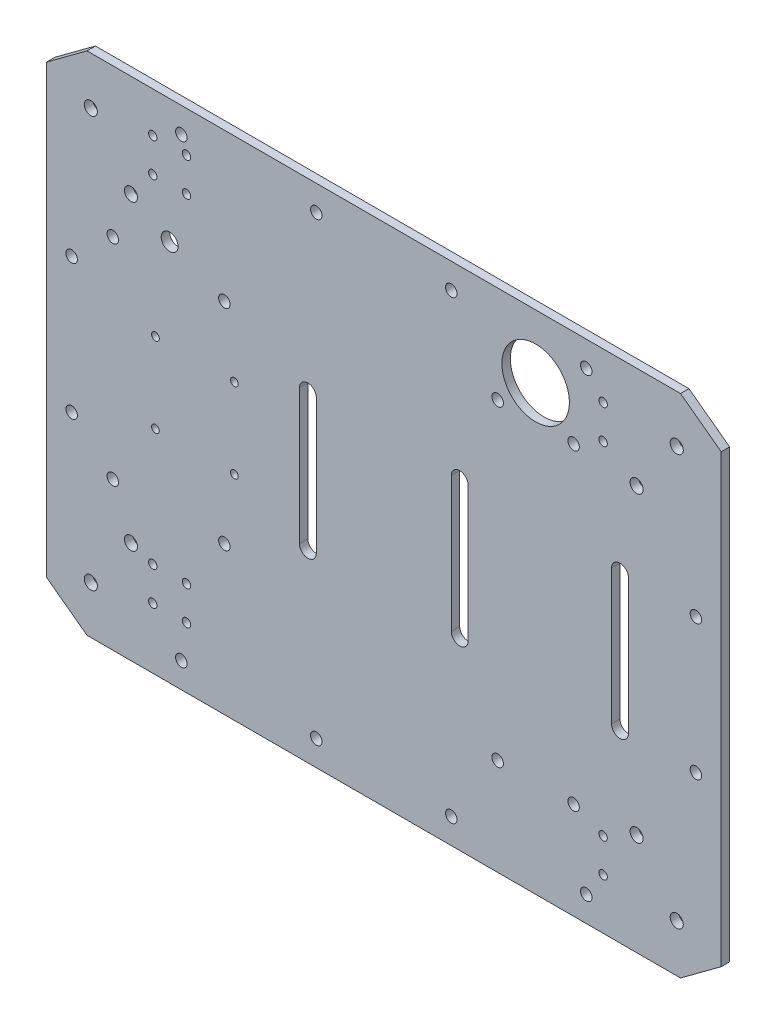
SolidWorks part; units mm, degrees
material "Thornel Mat VMA"
ref_plane "Front Plane" through (0, 0, 0) normal (0, 0, 1) x (1, 0, 0)
ref_plane "Top Plane" through (0, 0, 0) normal (0, 1, 0) x (1, 0, 0)
ref_plane "Right Plane" through (0, 0, 0) normal (1, 0, 0) x (0, 0, -1)
sketch "Sketch1" plane through (0, 0, 0) normal (0, 0, 1) x (1, 0, 0)
  line L0 (-127, 0) -> (127, 0) construction
  line L1 (0, -95.25) -> (0, 95.25) construction
  line L2 (-107.95, 0) -> (-107.95, 41.011) construction
  line L3 (-107.95, 41.011) -> (-95.25, 41.011) construction
  line L4 (-95.25, 41.011) -> (-79.9365, 52.3423) construction
  line L5 (-79.9365, 52.3423) -> (-79.9365, 76.2) construction
  line L6 (-79.9365, 76.2) -> (0, 76.2) construction
  line L7 (-95.25, 41.011) -> (-127, 83.9186) construction
  line L8 (-79.9365, 52.3423) -> (-111.6865, 95.25) construction
  line L9 (-111.6865, -95.25) -> (-127, -83.9186)
  line L10 (111.6865, -95.25) -> (127, -83.9186)
  line L11 (111.6865, 95.25) -> (127, 83.9186)
  line L12 (-87.5933, 46.6767) -> (-95.1475, 56.8856) construction
  line L13 (-95.1475, 56.8856) -> (-110.256, 77.3036) construction
  line L24 (127, -83.9186) -> (127, 83.9186)
  line L26 (111.6865, 95.25) -> (-111.6865, 95.25)
  line L27 (-111.6865, 95.25) -> (-127, 83.9186)
  line L28 (-127, 83.9186) -> (-127, -83.9186)
  line L30 (-111.6865, -95.25) -> (111.6865, -95.25)
  circle A0 centre (-95.1475, 56.8856) radius 2.4638
  circle A1 centre (-110.256, 77.3036) radius 2.4638
  circle A2 centre (110.256, 77.3036) radius 2.4638
  circle A3 centre (95.1475, 56.8856) radius 2.4638
  circle A4 centre (-110.256, -77.3036) radius 2.4638
  circle A5 centre (-95.1475, -56.8856) radius 2.4638
  circle A6 centre (110.256, -77.3036) radius 2.4638
  circle A7 centre (95.1475, -56.8856) radius 2.4638
  point P12 (0, 0)
  dimension "D1" = 190.5
  dimension "D2" = 254
  dimension "D3" = 19.05
  dimension "D4" = 19.05
  dimension "D5" = 12.7
  dimension "D6" = 19.05
  dimension "D7" = 143.5
  dimension "D8" = 12.7
  dimension "D9" = 25.4
extrude "Boss-Extrude1" add sketch "Sketch1" along normal blind 3.175
sketch "Sketch2" plane through (0, 0, 3.175) normal (0, 0, 1) x (1, 0, 0)
  line L0 (-127, 0) -> (127, 0) construction
  line L1 (-127, 83.9186) -> (-127, -83.9186) construction
  line L2 (127, -83.9186) -> (127, 83.9186) construction
  line L3 (57.15, 65.0875) -> (57.15, -65.0875) construction
  line L4 (38.1, 65.0875) -> (76.2, 65.0875)
  line L5 (38.1, 65.0875) -> (38.1, -65.0875)
  line L6 (38.1, -65.0875) -> (76.2, -65.0875)
  line L7 (76.2, 65.0875) -> (76.2, -65.0875)
  line L8 (38.1, 65.0875) -> (76.2, -65.0875) construction
  line L9 (38.1, -65.0875) -> (76.2, 65.0875) construction
  line L10 (57.15, 58.7375) -> (47.625, 58.7375) construction
  line L11 (47.625, 58.7375) -> (38.1, 58.7375) construction
  circle A0 centre (42.8625, 58.7375) radius 2.159
  circle A1 centre (42.8625, -58.7375) radius 2.159
  circle A2 centre (71.4375, -58.7375) radius 2.159
  circle A3 centre (71.4375, 58.7375) radius 2.159
  point P6 (57.15, 0)
  point P17 (42.8625, 58.7375)
  dimension "D1" = 38.1
  dimension "D2" = 130.175
  dimension "D3" = 6.35
  dimension "D4" = 9.525
  dimension "D5" = 69.85
extrude "Cut-Extrude1" cut sketch "Sketch2" against normal through all contours A1 | A2 | A3 | A0 region at (42.8625, 58.7375, 3.175) region at (42.8625, -58.7375, 3.175) region at (71.4375, -58.7375, 3.175) region at (71.4375, 58.7375, 3.175)
sketch "Sketch3" plane through (0, 0, 3.175) normal (0, 0, 1) x (1, 0, 0)
  line L0 (0, 95.25) -> (0, -95.25) construction
  line L1 (111.6865, 95.25) -> (-111.6865, 95.25) construction
  line L2 (-111.6865, -95.25) -> (111.6865, -95.25) construction
  line L3 (127, 0) -> (-127, 0) construction
  line L4 (127, -83.9186) -> (127, 83.9186) construction
  line L5 (-127, 83.9186) -> (-127, -83.9186) construction
  line L8 (119.3433, -89.5843) -> (111.789, -79.3753) construction
  line L10 (111.6865, -95.25) -> (127, -83.9186) construction
  line L11 (111.6865, -95.25) -> (127, -83.9186)
  circle A0 centre (111.789, -79.3753) radius 1.9844
  circle A1 centre (96.6805, -58.9574) radius 1.9844
  dimension "D2" = 3.9688
  dimension "D3" = 3.9688
  dimension "D1" = 12.7
  dimension "D4" = 25.4
sketch "Sketch5" plane through (0, 0, 0) normal (0, 0, -1) x (-1, 0, 0)
  line L0 (-127, 0) -> (127, 0) construction
  line L1 (105.9946, 43.5) -> (55.9947, 43.5) construction
  line L2 (105.9946, 43.5) -> (105.9946, -43.5) construction
  line L3 (105.9946, -43.5) -> (55.9947, -43.5) construction
  line L4 (55.9947, 43.5) -> (55.9947, -43.5) construction
  line L5 (89.2369, 18.0341) -> (89.2369, -18.0339)
  line L7 (-71.4375, 58.7375) -> (-42.8625, 58.7375) construction
  line L8 (0, 64.0679) -> (0, -49.8393) construction
  line L9 (-47.625, 22.225) -> (47.625, 22.225) construction
  line L10 (-47.625, 22.225) -> (-47.625, -22.225) construction
  line L11 (-47.625, -22.225) -> (47.625, -22.225) construction
  line L12 (47.625, 22.225) -> (47.625, -22.225) construction
  line L13 (-47.625, 22.225) -> (47.625, -22.225) construction
  line L14 (-47.625, -22.225) -> (47.625, 22.225) construction
  line L15 (-88.9, 25.4) -> (-88.9, -25.4) construction
  line L16 (-85.725, 25.4) -> (-85.725, -25.4)
  line L17 (-92.075, 25.4) -> (-92.075, -25.4)
  line L18 (111.6865, -95.25) -> (-111.6865, -95.25) construction
  line L19 (-28.575, 25.4) -> (-28.575, -25.4) construction
  line L21 (-127, -83.9186) -> (-127, 83.9186) construction
  line L22 (-57.15, 71.4375) -> (80.5946, 71.4375) construction
  line L23 (80.5946, 71.4375) -> (80.5946, 48.58) construction
  line L24 (-127, -83.9186) -> (-127, 83.9186) construction
  line L25 (80.5946, -77.0458) -> (80.5946, 48.58) construction
  line L26 (127, 0) -> (-127, 0) construction
  line L27 (80.9947, 0) -> (80.9947, -8419.0368) construction
  line L28 (-25.4, 25.4) -> (-25.4, -25.4)
  line L29 (-31.75, 25.4) -> (-31.75, -25.4)
  line L30 (28.575, 25.4) -> (28.575, -25.4) construction
  line L31 (25.4, 25.4) -> (25.4, -25.4)
  line L32 (31.75, 25.4) -> (31.75, -25.4)
  line L33 (71.0787, 0) -> (71.0787, 12.3782) construction
  line L34 (53.2197, 18.0341) -> (89.2369, 18.0341)
  line L35 (53.2197, 18.0341) -> (53.2197, -18.0339)
  line L36 (53.2197, -18.0339) -> (89.2369, -18.0339)
  line L40 (-57.15, 58.7375) -> (-57.15, 95.25) construction
  line L41 (-111.6865, 95.25) -> (111.6865, 95.25) construction
  arc A0 (-85.725, 25.4) -> (-92.075, 25.4) centre (-88.9, 25.4) ccw
  arc A1 (-92.075, -25.4) -> (-85.725, -25.4) centre (-88.9, -25.4) ccw
  circle A2 centre (80.5946, 48.58) radius 3.175
  circle A3 centre (-57.15, 71.4375) radius 12.7
  circle A4 centre (74.2446, 67.31) radius 1.5875
  circle A5 centre (74.2446, 80.01) radius 1.5875
  circle A6 centre (74.2446, -72.39) radius 1.5875
  circle A7 centre (74.2446, -59.69) radius 1.5875
  circle A8 centre (86.9446, -72.39) radius 1.5875
  circle A9 centre (86.9446, -59.69) radius 1.5875
  circle A10 centre (86.9446, 80.01) radius 1.5875
  circle A11 centre (86.9446, 67.31) radius 1.5875
  circle A12 centre (59.9952, 39.4995) radius 2.159
  circle A13 centre (101.9941, 39.4995) radius 2.159
  circle A14 centre (59.9952, -39.4995) radius 2.159
  circle A15 centre (101.9941, -39.4995) radius 2.159
  circle A16 centre (-82.55, -63.4824) radius 1.5875
  circle A17 centre (-82.55, -76.1824) radius 1.5875
  circle A18 centre (-82.55, 77.7875) radius 1.5875
  circle A19 centre (-82.55, 65.0875) radius 1.5875
  arc A20 (-25.4, 25.4) -> (-31.75, 25.4) centre (-28.575, 25.4) ccw
  arc A21 (-31.75, -25.4) -> (-25.4, -25.4) centre (-28.575, -25.4) ccw
  arc A22 (25.4, 25.4) -> (31.75, 25.4) centre (28.575, 25.4) cw
  arc A23 (31.75, -25.4) -> (25.4, -25.4) centre (28.575, -25.4) cw
  circle A24 centre (56.2197, 15.0341) radius 1.4478
  circle A25 centre (56.2197, -15.0341) radius 1.4478
  circle A26 centre (85.9377, -15.0341) radius 1.4478
  circle A27 centre (85.9377, 15.0341) radius 1.4478
  point P0 (80.9947, 0)
  point P9 (0, 0)
  point P16 (-88.9, 0)
  point P77 (-28.575, 0)
  point P84 (28.575, 0)
  point P89 (71.0787, 0)
  dimension "D10" = 6.35
  dimension "D15" = 2.9997
  dimension "D17" = 3.175
  dimension "D18" = 3.175
  dimension "D21" = 3.175
  dimension "D22" = 3.175
  dimension "D25" = 4.0005
  dimension "D28" = 3.175
  dimension "D29" = 3.175
  dimension "D30" = 12.7
  dimension "D33" = 3.175
  dimension "D34" = 3.175
  dimension "D45" = 2.8956
  dimension "D9" = 15.24
  dimension "D13" = 14.859
  dimension "D14" = 3
  dimension "D1" = 87.0001
  dimension "D2" = 49.9999
  dimension "D4" = 44.45
  dimension "D5" = 95.25
  dimension "D6" = 50.8
  dimension "D7" = 6.35
  dimension "D8" = 38.1
  dimension "D11" = 5.08
  dimension "D12" = 25.4
  dimension "D16" = 12.7
  dimension "D19" = 6.35
  dimension "D23" = 12.7
  dimension "D24" = 22.86
  dimension "D26" = 4.0005
  dimension "D32" = 44.45
  dimension "D35" = 12.7
  dimension "D36" = 6.35
  dimension "D37" = 44.45
  dimension "D38" = 50.8
  dimension "D39" = 6.35
  dimension "D40" = 28.575
  dimension "D41" = 36.0172
  dimension "D42" = 36.068
  dimension "D44" = 3
extrude "Cut-Extrude2" cut sketch "Sketch5" against normal through all contours A3 | A2 | A5 | A4 | A6 | A7 | A8 | A9 | A10 | A11 | A14 | A15 | A13 | A12 | A19 | A18 | A17 | A16 | L29 A21 L28 A20 | A23 L4 A22 L31 | A23 L32 A22 L4 | A27 | A24 | A25 | A26 | L17 A1 L16 A0 | A4 | A19 region at (88.9, 0, 0) region at (28.575, 0, 0) region at (-28.575, 0, 0) region at (-80.5946, 48.58, 0) region at (57.15, 71.4375, 0) region at (-74.2446, 67.31, 0) region at (-74.2446, 80.01, 0) region at (-74.2446, -72.39, 0) region at (-74.2446, -59.69, 0) region at (-86.9446, -72.39, 0) region at (-86.9446, -59.69, 0) region at (-86.9446, 80.01, 0) region at (-86.9446, 67.31, 0) region at (-59.9952, 39.4995, 0) region at (-101.9941, 39.4995, 0) region at (-59.9952, -39.4995, 0) region at (-101.9941, -39.4995, 0) region at (82.55, -63.4824, 0) region at (82.55, -76.1824, 0) region at (82.55, 77.7875, 0) region at (82.55, 65.0875, 0) region at (-56.2197, 15.0341, 0) region at (-56.2197, -15.0341, 0) region at (-85.9377, -15.0341, 0) region at (-85.9377, 15.0341, 0)
sketch "Sketch6" plane through (0, 0, 0) normal (0, 0, -1) x (-1, 0, 0)
  line L0 (0, 0) -> (-135.1326, 0) construction
  line L1 (0, 0) -> (0, -95.25) construction
  line L2 (111.6865, -95.25) -> (-111.6865, -95.25) construction
  line L3 (-76.2, -95.25) -> (-76.2, -85.725) construction
  line L4 (117.475, 0) -> (117.475, -25.4) construction
  line L5 (127, 0) -> (-127, 0) construction
  line L6 (127, 83.9186) -> (127, -83.9186) construction
  circle A0 centre (-76.2, -85.725) radius 2.159
  circle A1 centre (-25.4, -85.725) radius 2.159
  circle A2 centre (25.4, -85.725) radius 2.159
  circle A3 centre (76.2, -85.725) radius 2.159
  circle A4 centre (76.2, 85.725) radius 2.159
  circle A5 centre (25.4, 85.725) radius 2.159
  circle A6 centre (-25.4, 85.725) radius 2.159
  circle A7 centre (-76.2, 85.725) radius 2.159
  circle A8 centre (117.475, -25.4) radius 2.159
  circle A9 centre (117.475, 25.4) radius 2.159
  circle A10 centre (-117.475, 25.4) radius 2.159
  circle A11 centre (-117.475, -25.4) radius 2.159
  dimension "D2" = 9.525
  dimension "D3" = 76.2
  dimension "D5" = 9.525
  dimension "D6" = 25.4
  dimension "D4" = 4
extrude "Cut-Extrude3" cut sketch "Sketch6" against normal through all
